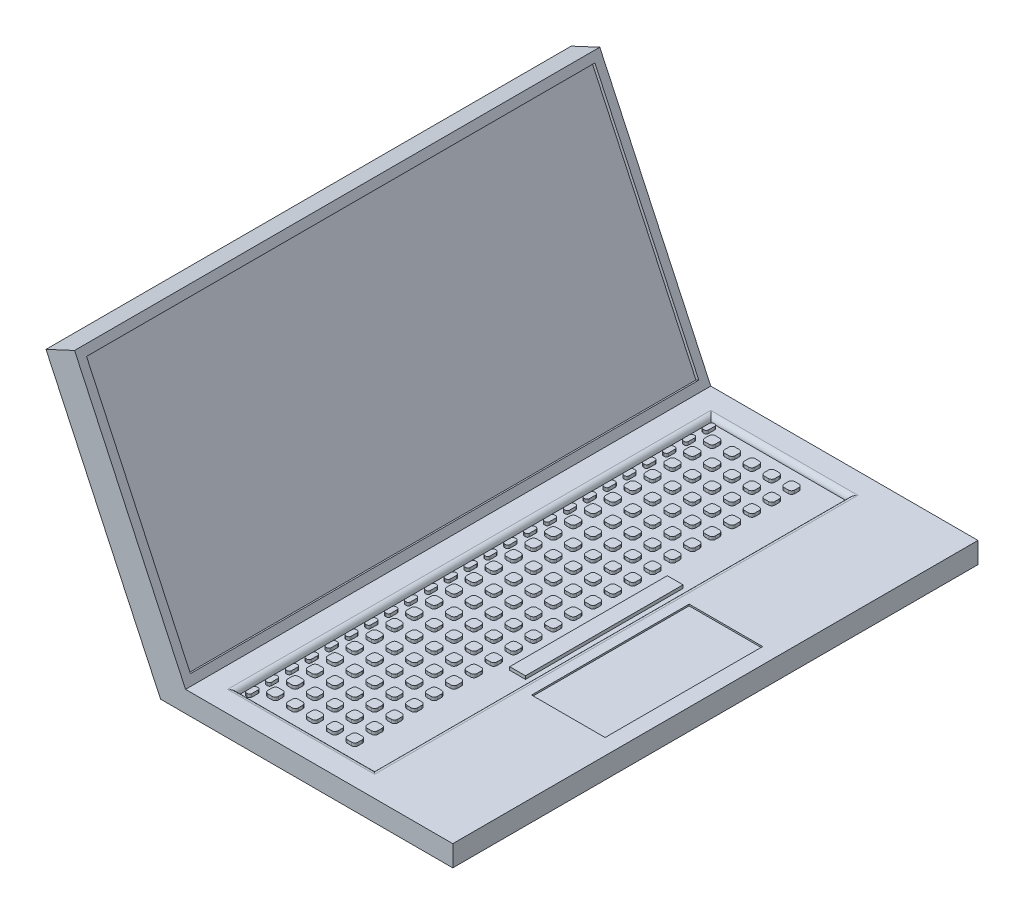
SolidWorks part; units mm, degrees
ref_plane "Plan de face" through (0, 0, 0) normal (0, 0, 1) x (1, 0, 0)
ref_plane "Plan de dessus" through (0, 0, 0) normal (0, 1, 0) x (1, 0, 0)
ref_plane "Plan de droite" through (0, 0, 0) normal (1, 0, 0) x (0, 0, -1)
sketch "Esquisse1" plane through (0, 0, 0) normal (0, 0, 1) x (1, 0, 0)
  line L0 (0, 0) -> (-27.8167, 0)
  line L1 (-27.8167, 0) -> (-38.7235, 23.3898)
  line L2 (-38.7235, 23.3898) -> (-36.0046, 24.6577)
  line L3 (-36.0046, 24.6577) -> (-25.4391, 2)
  line L4 (-25.4391, 2) -> (0, 2)
  line L5 (0, 2) -> (0, 0)
  dimension "D1" = 3
  dimension "D2" = 25
  dimension "D3" = 2
  dimension "D4" = 115
extrude "Boss.-Extru.1" add sketch "Esquisse1" along normal blind 50
sketch "Esquisse2" plane through (0, 2, 0) normal (0, 1, 0) x (1, 0, 0)
  line L0 (0, -50) -> (-25.4391, -50) construction
  line L1 (-9.9391, -47.5) -> (-22.9391, -47.5)
  line L2 (-9.9391, -47.5) -> (-9.9391, -2.5)
  line L3 (-9.9391, -2.5) -> (-22.9391, -2.5)
  line L4 (-22.9391, -47.5) -> (-22.9391, -2.5)
  line L5 (-9.9391, -47.5) -> (-22.9391, -2.5) construction
  line L6 (-9.9391, -2.5) -> (-22.9391, -47.5) construction
  line L7 (0, 0) -> (-25.4391, 0) construction
  line L8 (-25.4391, -50) -> (-25.4391, 0) construction
  point P0 (-16.4391, -25)
  dimension "D1" = 2.5
  dimension "D2" = 2.5
  dimension "D3" = 2.5
  dimension "D4" = 13
extrude "Enlèv. mat.-Extru.1" cut sketch "Esquisse2" against normal blind 0.5
fillet "Congé1" radius 0.5 4 edges at (-16.4391, 2, 2.5) (-9.9391, 2, 25) (-16.4391, 2, 47.5) (-22.9391, 2, 25)
sketch "Esquisse3" plane through (0, 1.5, 0) normal (0, 1, 0) x (1, 0, 0)
  line L0 (-22.4391, -47.2) -> (-22.3391, -47.2)
  line L1 (-22.1391, -47) -> (-22.1391, -46.4)
  line L2 (-22.3391, -46.2) -> (-22.4391, -46.2)
  line L3 (-22.6391, -46.4) -> (-22.6391, -47)
  line L4 (-22.9391, -2.5) -> (-22.9391, -47.5) construction
  line L5 (-22.9391, -47.5) -> (-9.9391, -47.5) construction
  arc A0 (-22.4391, -47.2) -> (-22.6391, -47) centre (-22.4391, -47) cw
  arc A1 (-22.3391, -47.2) -> (-22.1391, -47) centre (-22.3391, -47) ccw
  arc A2 (-22.1391, -46.4) -> (-22.3391, -46.2) centre (-22.3391, -46.4) ccw
  arc A3 (-22.4391, -46.2) -> (-22.6391, -46.4) centre (-22.4391, -46.4) ccw
  point P12 (-22.1391, -47.2)
  point P15 (-22.1391, -46.2)
  point P18 (-22.6391, -46.2)
  dimension "D5" = 0.2
  dimension "D1" = 1
  dimension "D2" = 0.5
  dimension "D3" = 0.3
  dimension "D4" = 0.3
extrude "Boss.-Extru.2" add sketch "Esquisse3" along normal blind 0.3
pattern_linear "Répétition linéaire1" count 24 spacing 1.89 along (0, 0, -1) of "Boss.-Extru.2"
sketch "Esquisse4" plane through (0, 1.5, 0) normal (0, 1, 0) x (1, 0, 0)
  line L0 (-21.3391, -46.25) -> (-20.9391, -46.25)
  line L1 (-20.6391, -45.95) -> (-20.6391, -45.55)
  line L2 (-20.9391, -45.25) -> (-21.3391, -45.25)
  line L3 (-21.6391, -45.55) -> (-21.6391, -45.95)
  line L4 (-22.9391, -47.5) -> (-9.9391, -47.5) construction
  line L5 (-22.1391, -45.11) -> (-22.1391, -44.51) construction
  arc A0 (-20.9391, -46.25) -> (-20.6391, -45.95) centre (-20.9391, -45.95) ccw
  arc A1 (-21.3391, -46.25) -> (-21.6391, -45.95) centre (-21.3391, -45.95) cw
  arc A2 (-21.3391, -45.25) -> (-21.6391, -45.55) centre (-21.3391, -45.55) ccw
  arc A3 (-20.6391, -45.55) -> (-20.9391, -45.25) centre (-20.9391, -45.55) ccw
  point P12 (-21.6391, -46.25)
  point P15 (-21.6391, -45.25)
  point P18 (-20.6391, -45.25)
  dimension "D5" = 0.3
  dimension "D1" = 1
  dimension "D2" = 1
  dimension "D3" = 1.25
  dimension "D4" = 0.5
extrude "Boss.-Extru.3" add sketch "Esquisse4" along normal blind 0.3
pattern_linear "Répétition linéaire2" count 23 spacing 1.89 along (0, 0, -1) of "Boss.-Extru.3"
pattern_linear "Répétition linéaire3" count 5 spacing 1.89 along (1, 0, 0) of "Répétition linéaire2"
sketch "Esquisse5" plane through (0, 1.5, 0) normal (0, 1, 0) x (1, 0, 0)
  line L0 (-12.0791, -17.5) -> (-10.5791, -17.5)
  line L1 (-10.5791, -17.5) -> (-10.5791, -32.5)
  line L2 (-10.5791, -32.5) -> (-12.0791, -32.5)
  line L3 (-12.0791, -32.5) -> (-12.0791, -17.5)
  line L4 (-22.9391, -47.5) -> (-9.9391, -47.5) construction
  line L5 (-13.0791, -27.05) -> (-13.0791, -26.65) construction
  dimension "D1" = 15
  dimension "D2" = 1.5
  dimension "D3" = 15
  dimension "D4" = 1
extrude "Boss.-Extru.4" add sketch "Esquisse5" along normal blind 0.3
sketch "Esquisse6" plane through (0, 2, 0) normal (0, 1, 0) x (1, 0, 0)
  line L0 (0, -50) -> (-25.4391, -50) construction
  line L1 (-8.5, -34) -> (-1.5, -34)
  line L2 (-8.5, -34) -> (-8.5, -19)
  line L3 (-8.5, -19) -> (-1.5, -19)
  line L4 (-1.5, -34) -> (-1.5, -19)
  line L5 (-8.5, -34) -> (-1.5, -19) construction
  line L6 (-8.5, -19) -> (-1.5, -34) construction
  line L7 (0, -50) -> (0, 0) construction
  point P0 (-5, -26.5)
  dimension "D1" = 15
  dimension "D2" = 7
  dimension "D3" = 16
  dimension "D4" = 1.5
extrude "Enlèv. mat.-Extru.2" cut sketch "Esquisse6" against normal blind 0.15
sketch "Esquisse7" plane through (-20.1295, -9.3865, 0) normal (0.9063, 0.4226, 0) x (0, 0, -1)
  line L0 (-0.8, 13.3637) -> (-0.8, 36.7637)
  line L1 (-0.8, 36.7637) -> (-49.2, 36.7637)
  line L2 (-49.2, 36.7637) -> (-49.2, 13.3637)
  line L3 (-49.2, 13.3637) -> (-0.8, 13.3637)
  line L4 (0, 12.5637) -> (0, 37.5637)
  line L5 (0, 37.5637) -> (-50, 37.5637)
  line L6 (-50, 37.5637) -> (-50, 12.5637)
  line L7 (-50, 12.5637) -> (0, 12.5637)
  line L8 (0, 12.5637) -> (0, 37.5637)
  line L9 (0, 37.5637) -> (-50, 37.5637)
  line L10 (-50, 37.5637) -> (-50, 12.5637)
  line L11 (-50, 12.5637) -> (0, 12.5637)
  dimension "D1" = 0
  dimension "D2" = 0.8
extrude "Enlèv. mat.-Extru.3" cut sketch "Esquisse7" against normal blind 0.3 contours L0 L1 L2 L3
